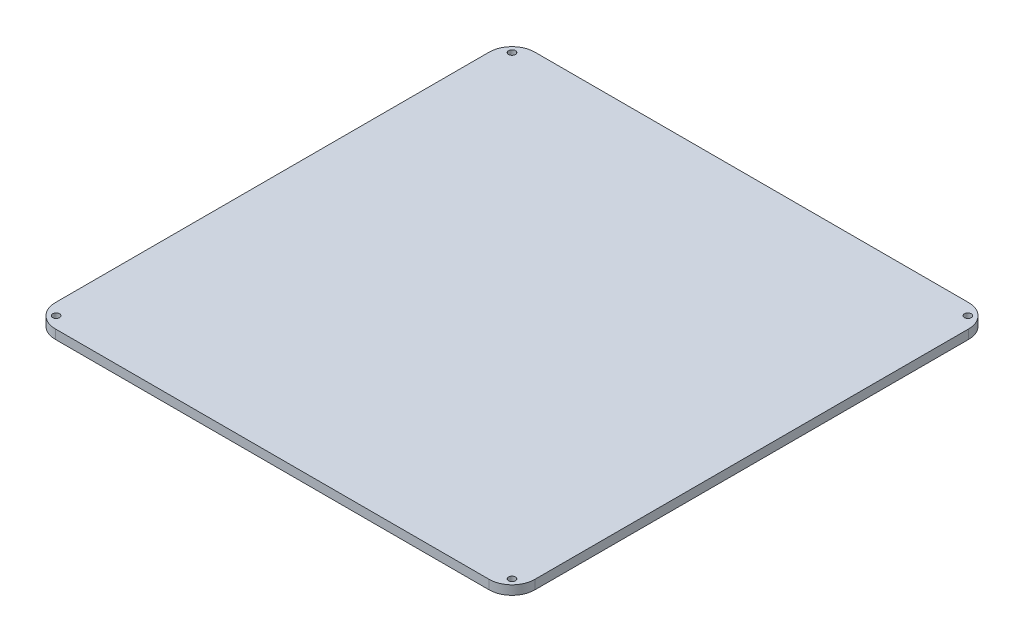
SolidWorks part; units mm, degrees
ref_plane "Front Plane" through (0, 0, 0) normal (0, 0, 1) x (1, 0, 0)
ref_plane "Top Plane" through (0, 0, 0) normal (0, 1, 0) x (1, 0, 0)
ref_plane "Right Plane" through (0, 0, 0) normal (1, 0, 0) x (0, 0, -1)
sketch "Sketch1" plane through (0, 0, 0) normal (0, 1, 0) x (1, 0, 0)
  line L0 (-101, -101) -> (-101, 101)
  line L5 (-105, -105) -> (105, -105)
  line L6 (-105, -105) -> (-105, 105)
  line L7 (-105, 105) -> (105, 105)
  line L8 (105, -105) -> (105, 105)
  line L9 (-101, 101) -> (101, 101)
  line L10 (101, -101) -> (101, 101)
  line L11 (-101, -101) -> (101, -101)
  line L12 (-101, 101) -> (-99.8333, 99.8333) construction
  line L13 (-55, 0) -> (55, 0) construction
  line L14 (-101, -101) -> (-99.8333, -99.8333) construction
  line L15 (0, -55) -> (0, 55) construction
  line L16 (101, -101) -> (99.8333, -99.8333) construction
  line L17 (101, 101) -> (99.8333, 99.8333) construction
  circle A1 centre (-99.8333, 99.8333) radius 1.5
  circle A2 centre (-99.8333, -99.8333) radius 1.5
  circle A3 centre (99.8333, -99.8333) radius 1.5
  circle A4 centre (99.8333, 99.8333) radius 1.5
  point P0 (0, 0)
  point P6 (-105, 0)
  point P7 (0, 105)
  dimension "D3" = 4
  dimension "D4" = 3
  dimension "D1" = 210
  dimension "D2" = 210
  dimension "D5" = 1.65
  dimension "D6" = 45
extrude "MainExtrude" add sketch "Sketch1" along normal blind 4 contours L6 L5 L8 L7
extrude "ScrewHoles" cut sketch "Sketch1<6>" along normal up to surface (4 mm away) contours A1 | A2 | A3 | A4 up to face at (0, 4, 0)
sketch "Sketch1<6>" plane through (0, 0, 0) normal (0, 1, 0) x (1, 0, 0) same geometry as "Sketch1"
fillet "RoundedCorners" radius 10 4 edges at (-105, 2, -105) (-105, 2, 105) (105, 2, -105) (105, 2, 105)
sketch "Sketch2" plane through (0, 0, 0) normal (0, -1, 0) x (1, 0, 0)
  line L0 (-17.92, 37.135) -> (17.92, 37.135) construction
  line L1 (2.2, 0) -> (-2.2, 0) construction
  circle A0 centre (-17.92, 37.135) radius 0.98
  circle A1 centre (-17.92, 37.135) radius 2
  circle A2 centre (17.92, 37.135) radius 2
  circle A3 centre (17.92, 37.135) radius 0.98
  circle A4 centre (-17.92, -37.135) radius 0.98
  circle A5 centre (-17.92, -37.135) radius 2
  circle A6 centre (17.92, -37.135) radius 0.98
  circle A7 centre (17.92, -37.135) radius 2
  point P3 (0, 37.135)
  dimension "D1" = 1.96
  dimension "D2" = 4
  dimension "D4" = 37.135
  dimension "D5" = 35.84
  dimension "D6" = 74.27
  dimension "D3" = 2
extrude "PCBHoles" add sketch "Sketch2" along normal blind 2
fillet "PCBRounds" radius 2 4 edges at (-17.92, 0, -35.135) (17.92, 0, -35.135) (17.92, 0, 39.135) (-17.92, 0, 39.135)
